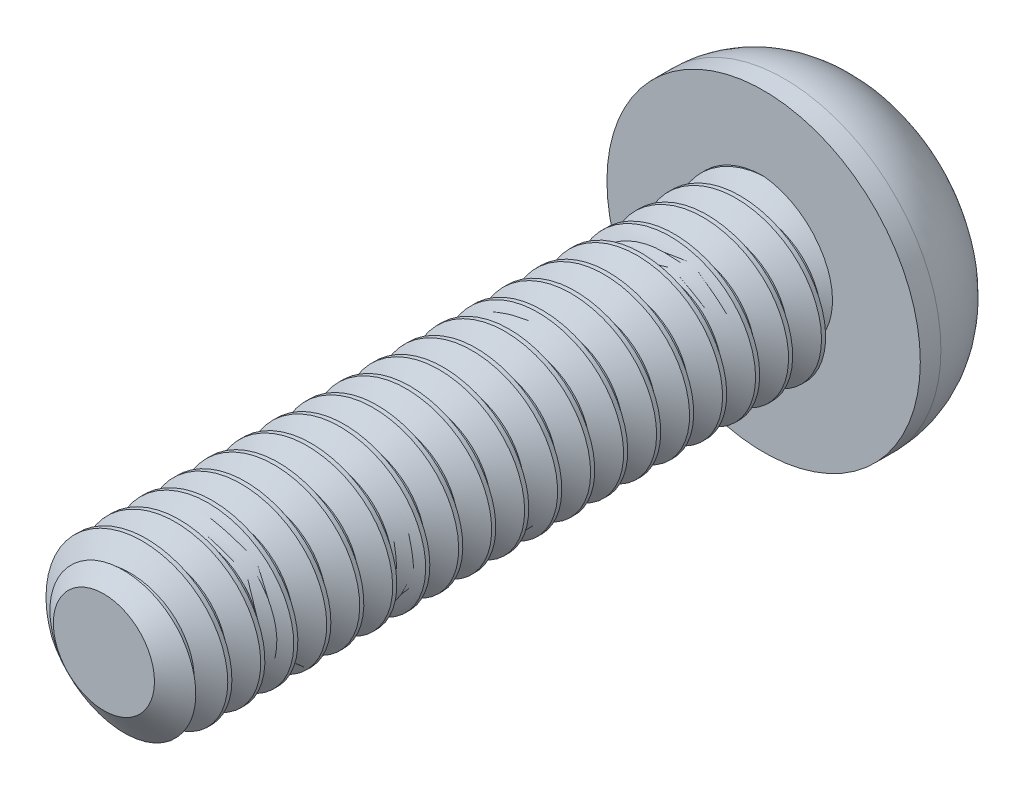
SolidWorks part; units mm, degrees
ref_plane "Front Plane" through (0, 0, 0) normal (0, 0, 1) x (1, 0, 0)
ref_plane "Top Plane" through (0, 0, 0) normal (0, 1, 0) x (1, 0, 0)
ref_plane "Right Plane" through (0, 0, 0) normal (1, 0, 0) x (0, 0, -1)
sketch "Sketch1" plane through (0, 0, 0) normal (0, 0, 1) x (1, 0, 0)
  circle A0 centre (0, 0) radius 2
  dimension "OD" = 4
extrude "Extrude1" add sketch "Sketch1" against normal blind 16
sketch "Sketch2" plane through (0, 0, 0) normal (0, 0, 1) x (1, 0, 0)
  circle A0 centre (0, 0) radius 2 construction
  circle A1 centre (0, 0) radius 2
curve "Helix/Spiral1" pitch 0.8 height 16.8 turns 21 parameters "pitch"=0.8
sketch "Sketch3" plane through (0, 0, 0) normal (1, 0, 0) x (0, 0, -1)
  line L0 (-0.7, 2) -> (-0.4, 1.4804)
  line L1 (-0.4, 1.4804) -> (-0.3, 1.4804)
  line L2 (-0.3, 1.4804) -> (0, 2)
  line L3 (-0.7, 2) -> (0, 2)
  line L4 (-0.35, 2) -> (-0.35, 1.4804) construction
  line L5 (-0.55, 1.7402) -> (-0.15, 1.7402) construction
  line L6 (0, 2) -> (0, -2) construction
  dimension "D1" = 0.1
  dimension "D2" = 0.4
  dimension "D3" = 60
sweep "Cut-Sweep1" cut profiles "Sketch3" path "Helix/Spiral1"
sketch "Sketch4" plane through (0, 0, 0) normal (1, 0, 0) x (0, 0, -1)
  line L0 (0.5417, 2) -> (0, 1.2264)
  line L1 (0, 1.2264) -> (0, 2)
  line L2 (0.5417, 2) -> (0, 2)
  line L3 (-0.7, 2) -> (0, 2) construction
  line L4 (0, 0) -> (7.0209, 0) construction
  dimension "D1" = 55
  dimension "D2" = 0.254
revolve "Cut-Revolve1" cut sketch "Sketch4" angle 360 about L4
sketch "Sketch5" plane through (0, 0, 0) normal (1, 0, 0) x (0, 0, -1)
  line L0 (16, -1.4947) -> (16, 1.4271) construction
  line L1 (16, 2.127) -> (28.1202, 2.127)
  line L2 (16, 2.127) -> (16, 0)
  line L3 (16, 0) -> (28, 0)
  line L4 (28, 1.7968) -> (28, 0)
  line L5 (28.1202, 2.127) -> (28, 1.7968)
  line L6 (0, 0) -> (9.9695, 0) construction
  point P3 (28, 2.127)
  point P10 (28, 2.127)
  dimension "D1" = 0.3302
  dimension "Thread min" = 28
  dimension "D2" = 0.127
  dimension "D3" = 20
sketch "Sketch6" plane through (0, 0, -16) normal (0, 0, -1) x (-1, 0, 0)
  circle A0 centre (0, 0) radius 3.8
  dimension "head dia" = 7.6
extrude "Extrude2" add sketch "Sketch6" along normal blind 2.75
sketch "Sketch10" plane through (0, 0, 0) normal (1, 0, 0) x (0, 0, -1)
  line L0 (18.75, -3.8) -> (18.75, 3.8) construction
  line L1 (0, 0) -> (15.9584, 0) construction
  line L2 (18.75, 3.8) -> (16, 3.8) construction
  line L3 (16, 3.8) -> (16, -3.8) construction
  line L4 (16.5, 3.8) -> (16.5, 4.3)
  line L5 (16.5, 4.3) -> (19.25, 4.3)
  line L6 (19.25, 4.3) -> (19.25, 1.5)
  line L7 (18.75, 1.5) -> (19.25, 1.5)
  arc A0 (18.75, 1.5) -> (16.5, 3.8) centre (16.4494, 1.5) ccw
  dimension "D1" = 3
  dimension "D2" = 0.5
  dimension "D3" = 0.5
revolve "Cut-Revolve2" cut sketch "Sketch10" angle 360 about L1
ref_plane "Plane1" through (0, 0, -18.75) normal (0, 0, 1) x (1, 0, 0)
sketch "Sketch7" plane through (0, 0, -18.75) normal (0, 0, -1) x (-1, 0, 0)
  line L1 (0, 1.7321) -> (-1.5, 0.866)
  line L2 (-1.5, 0.866) -> (-1.5, -0.866)
  line L3 (-1.5, -0.866) -> (0, -1.7321)
  line L4 (0, -1.7321) -> (1.5, -0.866)
  line L5 (1.5, -0.866) -> (1.5, 0.866)
  line L6 (1.5, 0.866) -> (0, 1.7321)
  circle A0 centre (0, 0) radius 1.5 construction
  dimension "hex dia" = 3
extrude "Cut-Extrude1" cut sketch "Sketch7" against normal blind 2.25
sketch "Sketch8" plane through (0, 0, -18.75) normal (0, 0, 1) x (1, 0, 0)
  circle A0 centre (0, 0) radius 1.7321
extrude "Cut-Extrude2" cut sketch "Sketch8" along normal through all draft 45
sketch "Sketch9" plane through (0, 0, 0) normal (1, 0, 0) x (0, 0, -1)
  line L0 (0, 2) -> (0, -2) construction
  line L1 (4.4, 2) -> (4.4, -2) construction
  dimension "D1" = 4.4
equation "\"D3@Helix/Spiral1\" = \"screw length@Extrude1\"+\"pitch@Helix/Spiral1\""
equation "\"D1@Sketch3\" = \"pitch@Helix/Spiral1\"*.125"
equation "\"D2@Sketch3\" = \"pitch@Helix/Spiral1\"*.5"
equation "\"D1@Cut-Extrude1\" = \"hex dia@Sketch7\"*.75"
equation "\"D1@Sketch9\" = \"pitch@Helix/Spiral1\"*5.5"
equation "\"D1@Sketch10\" = \"hex dia@Sketch7\""
equation "\"D1@Plane1\" = \"head depth@Extrude2\""
